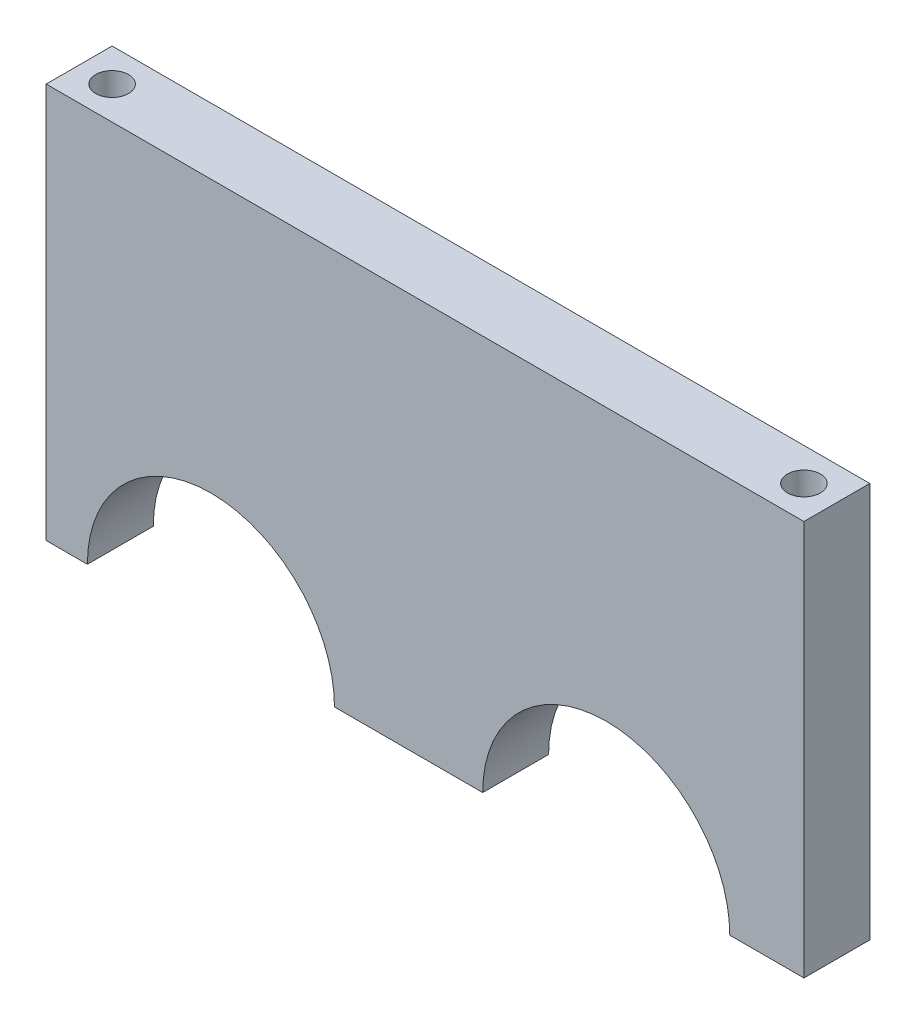
SolidWorks part; units mm, degrees
ref_plane "Front Plane" through (0, 0, 0) normal (0, 0, 1) x (1, 0, 0)
ref_plane "Top Plane" through (0, 0, 0) normal (0, 1, 0) x (1, 0, 0)
ref_plane "Right Plane" through (0, 0, 0) normal (1, 0, 0) x (0, 0, -1)
sketch "Sketch1" plane through (0, 0, 0) normal (0, 0, 1) x (1, 0, 0)
  line L1 (0, 0) -> (230, 0)
  line L2 (0, 0) -> (0, 120)
  line L3 (0, 120) -> (230, 120)
  line L4 (230, 0) -> (230, 120)
  dimension "D1" = 230
  dimension "D2" = 120
extrude "Boss-Extrude1" add sketch "Sketch1" along normal blind 20
sketch "Sketch2" plane through (0, 0, 20) normal (0, 0, 1) x (1, 0, 0)
  line L0 (0, 0) -> (230, 0) construction
  line L1 (0, 120) -> (0, 0) construction
  line L2 (230, 0) -> (230, 120) construction
  circle A0 centre (50, 0) radius 37.5
  circle A1 centre (170, 0) radius 37.5
  dimension "D1" = 75
  dimension "D2" = 75
  dimension "D3" = 50
  dimension "D4" = 60
extrude "Cut-Extrude1" cut sketch "Sketch2" against normal through all
sketch "Sketch3" plane through (0, 120, 0) normal (0, 1, 0) x (1, 0, 0)
  line L0 (230, -20) -> (230, 0) construction
  line L1 (230, 0) -> (0, 0) construction
  line L2 (230, -20) -> (0, -20) construction
  line L4 (0, -20) -> (0, 0) construction
  circle A0 centre (220, -10) radius 5
  circle A1 centre (10, -10) radius 5
  dimension "D1" = 10
  dimension "D4" = 10
  dimension "D2" = 10
  dimension "D3" = 10
  dimension "D5" = 10
  dimension "D6" = 10
extrude "Cut-Extrude2" cut sketch "Sketch3" against normal blind 20
